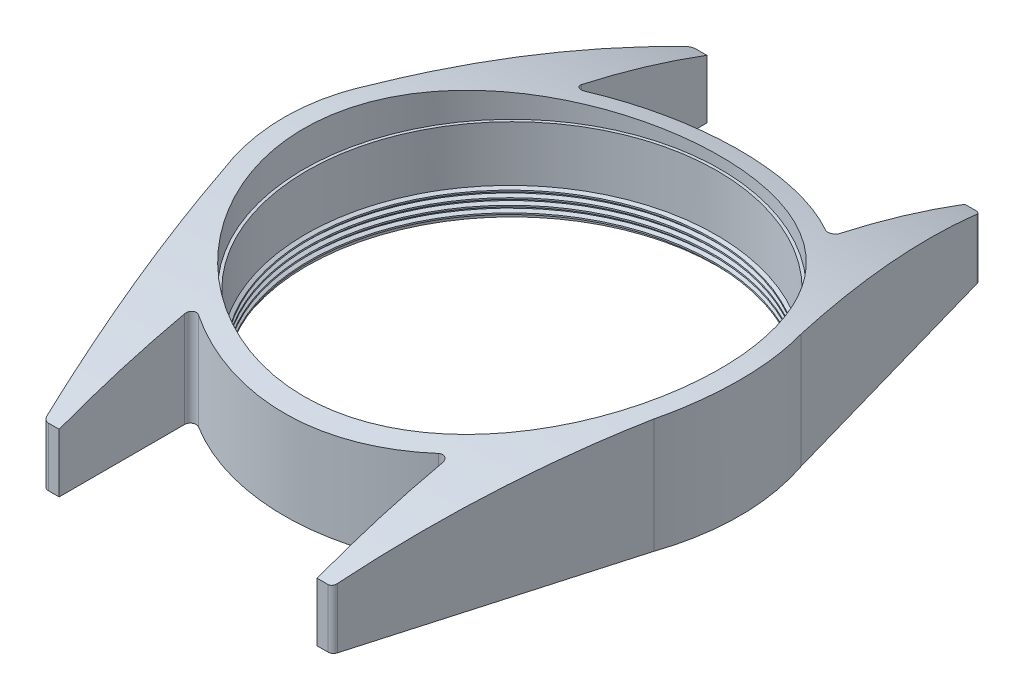
SolidWorks part; units mm, degrees
ref_plane "Front Plane" through (0, 0, 0) normal (0, 0, 1) x (1, 0, 0)
ref_plane "Top Plane" through (0, 0, 0) normal (0, 1, 0) x (1, 0, 0)
ref_plane "Right Plane" through (0, 0, 0) normal (1, 0, 0) x (0, 0, -1)
sketch "Sketch1" plane through (0, 0, 0) normal (0, 1, 0) x (1, 0, 0)
  line L0 (0, 19.42) -> (0, -25.4317) construction
  line L1 (-11, -16.9237) -> (-11, -19.0519) construction
  line L2 (-11, 21.9417) -> (-11, 16.9237) construction
  line L3 (-11, -16.9237) -> (-11, -27.6199)
  line L4 (-12.3857, -27.2699) -> (-18.38, -6.2699)
  line L7 (-11, 27.6199) -> (-11.9218, 27.6199)
  line L8 (-12.3857, 27.2699) -> (-18.38, 6.2699)
  line L9 (-11, -27.6199) -> (-11.9218, -27.6199)
  line L10 (-11, 16.9237) -> (-11, 27.6199)
  line L15 (11, 16.9237) -> (11, 27.6199)
  line L16 (11, 27.6199) -> (11.9218, 27.6199)
  line L17 (12.3857, 27.2699) -> (18.38, 6.2699)
  line L20 (11, -27.6199) -> (11.9218, -27.6199)
  line L21 (11, -16.9237) -> (11, -27.6199)
  line L22 (12.3857, -27.2699) -> (18.38, -6.2699)
  circle A5 centre (0, 0) radius 17.5
  arc A6 (-18.38, 6.2699) -> (-18.38, -6.2699) centre (0, 0) ccw
  arc A7 (-12.3857, 27.2699) -> (-11.9218, 27.6199) centre (-11.9218, 27.1375) cw
  arc A8 (-10.24, 16.5009) -> (-11, 16.9237) centre (-10.5024, 16.9237) cw
  arc A9 (18.38, 6.2699) -> (18.38, -6.2699) centre (0, 0) cw
  arc A10 (12.3857, 27.2699) -> (11.9218, 27.6199) centre (11.9218, 27.1375) ccw
  arc A13 (10.24, 16.5009) -> (11, 16.9237) centre (10.5024, 16.9237) ccw
  arc A14 (12.3857, -27.2699) -> (11.9218, -27.6199) centre (11.9218, -27.1375) cw
  arc A15 (10.24, -16.5009) -> (11, -16.9237) centre (10.5024, -16.9237) cw
  arc A17 (-10.24, -16.5009) -> (-11, -16.9237) centre (-10.5024, -16.9237) ccw
  arc A19 (-10.24, 16.5009) -> (10.24, 16.5009) centre (0, 0) cw
  arc A24 (10.24, -16.5009) -> (-10.24, -16.5009) centre (0, 0) cw
  arc A37 (-12.3857, -27.2699) -> (-11.9218, -27.6199) centre (-11.9218, -27.1375) ccw
  dimension "D1" = 35
  dimension "D2" = 38.84
  dimension "D6" = 0.35
  dimension "D7" = 0.76
  dimension "D3" = 11
extrude "Boss-Extrude1" add sketch "Sketch1" along normal blind 12
sketch3d "3DSketch1" plane through (0, 0, 0) normal (0, 0, 1) x (1, 0, 0)
  dimension "D1" = 30
sketch "Sketch6" plane through (30, 0, 0) normal (1, 0, 0) x (0, 0, -1)
  line L0 (-27.2699, 12) -> (-27.2699, 0) construction
  line L1 (6.2699, 12) -> (6.2699, 0) construction
  line L2 (27.2699, 12) -> (27.2699, 0) construction
  line L5 (-27.6199, 4.999) -> (-27.6199, 12)
  line L6 (-27.6199, 12) -> (-27.6199, 0) construction
  line L7 (-27.6199, 12) -> (27.6199, 12)
  line L8 (27.6199, 12) -> (27.6199, 4.999)
  line L9 (27.6199, 12) -> (27.6199, 0) construction
  arc A0 (27.6199, 4.999) -> (-27.6199, 4.999) centre (0, -68.2802) ccw
  point P0 (-27.2699, 5.13)
  point P1 (6.2699, 9.78)
  point P4 (27.2699, 5.13)
  dimension "D1" = 5.13
  dimension "D2" = 9.78
  dimension "D3" = 5.13
extrude "Cut-Extrude2" cut sketch "Sketch6" against normal through all
thread "Thread2" pitch 0.5 method extrude profile "Thread Profile3" start angle 0, offset 0, length 2.24, pitch 0.56, diameter 35
ref_plane "Plane4" through (17.5, 0, 0) normal (0, 0, 1) x (1, 0, 0)
sketch "Thread Profile3" plane through (17.5, 0, 0) normal (0, 0, 1) x (1, 0, 0)
  line L0 (0, 0) -> (0, 0.5) construction
  line L11 (0, 0) -> (0, 0.4375)
  line L12 (0, 0.4375) -> (-0.2706, 0.2812)
  line L13 (-0.2706, 0.2812) -> (-0.2706, 0.1562)
  line L15 (-0.2706, 0.1562) -> (0, 0)
  line L17 (-0.2706, 0.2187) -> (0, 0.2187) construction
  point P2 (0, 0)
  dimension "Pitch" = 0.5
  dimension "Profile_Angle" = 60
  dimension "Profile_Land" = 0.125
  dimension "Profile_Height" = 0.2706
ref_plane "Plane5" through (0, 10.03, 0) normal (0, 1, 0) x (1, 0, 0)
sketch "Sketch14" plane through (0, 10.03, 0) normal (0, 1, 0) x (1, 0, 0)
  circle A0 centre (0, 0) radius 17.75
  dimension "D1" = 35.5
extrude "Cut-Extrude3" cut sketch "Sketch14" against normal mid plane 6
